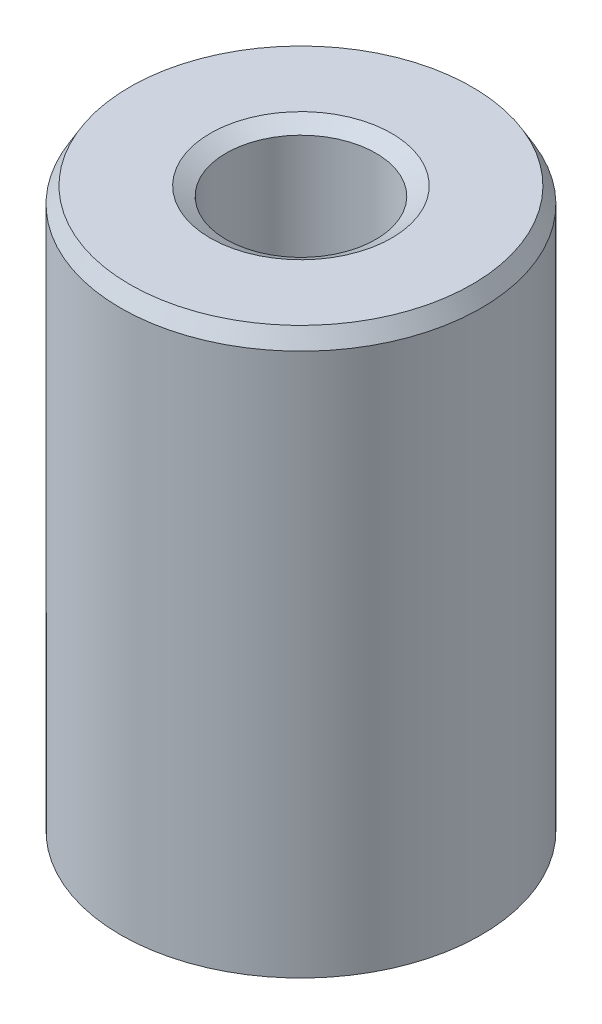
SolidWorks part; units mm, degrees
ref_plane "Front Plane" through (0, 0, 0) normal (0, 0, 1) x (1, 0, 0)
ref_plane "Top Plane" through (0, 0, 0) normal (0, 1, 0) x (1, 0, 0)
ref_plane "Right Plane" through (0, 0, 0) normal (1, 0, 0) x (0, 0, -1)
sketch "Sketch1" plane through (0, 0, 0) normal (0, 1, 0) x (1, 0, 0)
  circle A0 centre (0, 0) radius 12.5
  dimension "SLEEVE_OD" = 25
extrude "Boss-Extrude1" add sketch "Sketch1" along normal blind 39.3767
sketch "Sketch2" plane through (0, 0, 0) normal (0, 1, 0) x (1, 0, 0)
  circle A0 centre (0, 0) radius 5.1904
  dimension "BORE_D" = 10.3807
extrude "Cut-Extrude1" cut sketch "Sketch2" along normal through all
chamfer "Chamfer1" distance 1.1014 angle 30 4 edges at (0, 39.3767, 5.1904) (0, 0, 5.1904) (0, 0, 12.5) (0, 39.3767, 12.5) first distance on face at (0, 39.3767, 5.1904) first distance on face at (0, 0, 5.1904) first distance on face at (0, 39.3767, 12.5)
